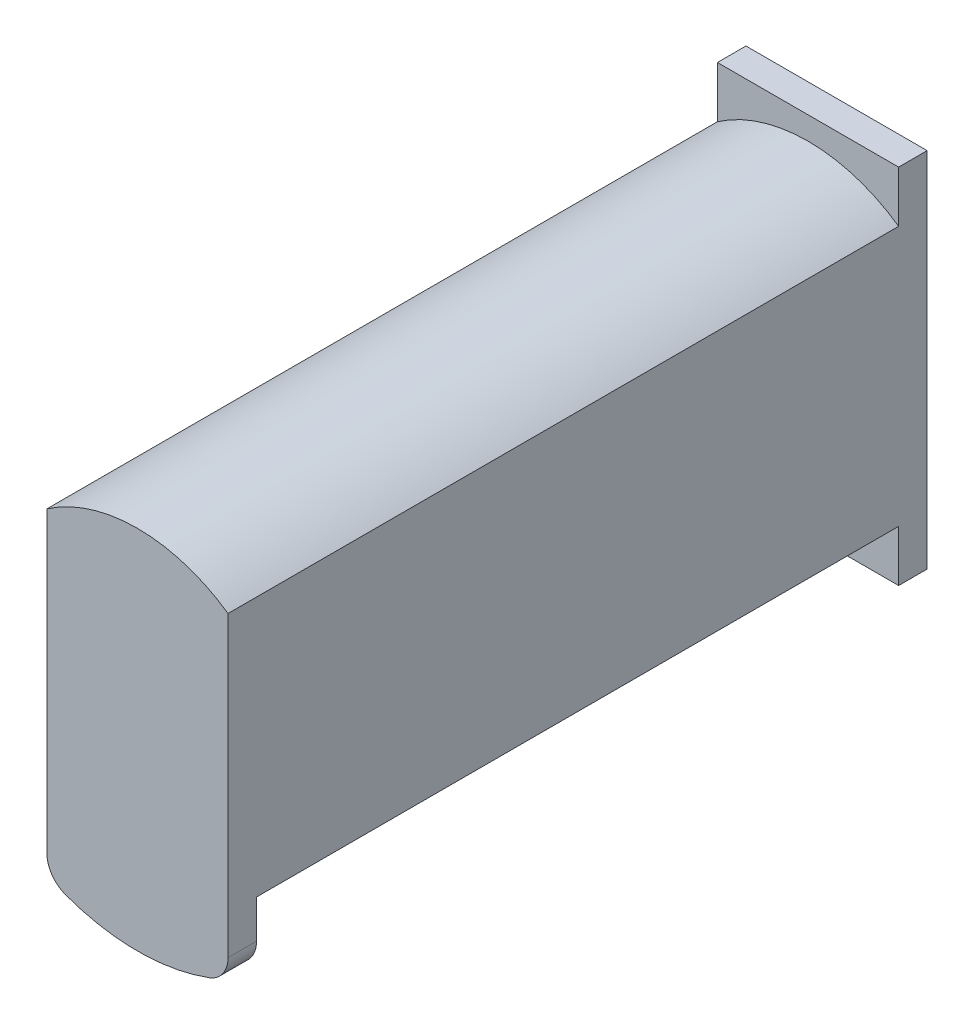
SolidWorks part; units mm, degrees
ref_plane "Front Plane" through (0, 0, 0) normal (0, 0, 1) x (1, 0, 0)
ref_plane "Top Plane" through (0, 0, 0) normal (0, 1, 0) x (1, 0, 0)
ref_plane "Right Plane" through (0, 0, 0) normal (1, 0, 0) x (0, 0, -1)
sketch "Sketch2" plane through (0, 0, 0) normal (0, 0, 1) x (1, 0, 0)
  line L0 (0, -12.7) -> (0, 12.7) construction
  line L1 (-12.7, -12.7) -> (-12.7, 12.7) construction
  line L2 (12.7, -12.7) -> (12.7, 12.7) construction
  line L6 (5.75, -6.2) -> (-5.75, -6.2)
  line L9 (5.75, -6.2) -> (5.75, -19.2)
  line L12 (5.75, -19.2) -> (-5.75, -19.2)
  line L15 (-12.7, 12.7) -> (12.7, 12.7)
  line L16 (12.7, -25.4) -> (-12.7, -25.4)
  line L17 (12.7, -25.4) -> (12.7, 25.4)
  line L18 (12.7, 25.4) -> (-12.7, 25.4)
  line L19 (-12.7, -25.4) -> (-12.7, 25.4)
  line L20 (12.7, -25.4) -> (-12.7, 25.4) construction
  line L21 (12.7, 25.4) -> (-12.7, -25.4) construction
  line L22 (-12.7, -12.7) -> (12.7, -12.7)
  line L23 (-5.75, -6.2) -> (-5.75, -19.2)
  line L24 (5.75, -6.2) -> (-5.75, -19.2) construction
  line L25 (5.75, -19.2) -> (-5.75, -6.2) construction
  line L26 (5.75, 19.2) -> (-5.75, 19.2)
  line L27 (5.75, 19.2) -> (5.75, 6.2)
  line L28 (5.75, 6.2) -> (-5.75, 6.2)
  line L29 (-5.75, 19.2) -> (-5.75, 6.2)
  line L30 (5.75, 19.2) -> (-5.75, 6.2) construction
  line L31 (5.75, 6.2) -> (-5.75, 19.2) construction
  arc A0 (-12.7, -12.7) -> (12.7, -12.7) centre (0, -12.7) ccw construction
  arc A1 (12.7, 12.7) -> (-12.7, 12.7) centre (0, 12.7) ccw construction
  circle A2 centre (0, 12.7) radius 3.5
  circle A3 centre (0, -12.7) radius 3.5
  arc A15 (-12.7, 18.2085) -> (12.7, 18.2085) centre (0, 0) cw
  arc A16 (-12.7, -18.2085) -> (12.7, -18.2085) centre (0, 0) ccw
  point P2 (0, 0)
  point P38 (0, 0)
  point P62 (0, 25.4)
  dimension "D3" = 7
  dimension "D4" = 13
  dimension "D5" = 11.5
  dimension "D11" = 69.79
  dimension "D12" = 22.2
  dimension "D13" = 22.2
  dimension "D1" = 25.4
  dimension "D2" = 25.4
extrude "Boss-Extrude4" add sketch "Sketch2" along normal blind 4 contours L18 L19 L16 L17 | A2 | A3
extrude "Boss-Extrude5" add sketch "Sketch2<4>" along normal blind 90 from surface contours L19 A16 L17 L22 L9 L12 L23 | A3 L22 L23 L12 L9 | A3 L22 L9 L6 L23 | L22 A3 | L22 A3 | L15 A2 | L15 A2 | A2 L15 L27 L26 L29 | A2 L15 L29 L28 L27 | L29 L15 L19 L22 L23 L6 L9 L17 L27 L28 | A15 L19 L15 L29 L26 L27 L17 region at (0, -8.8383, 0) region at (0, 0, 0) region at (9.225, -12.9712, 0) region at (0, -16.5617, 0) region at (0, -14.1854, 0) region at (0, -11.2146, 0) region at (9.225, 12.9712, 0) region at (0, 8.8383, 0) region at (0, 16.5617, 0) region at (0, 11.2146, 0) region at (0, 14.1854, 0) starting at face at (3.5, 12.7, 4)
sketch "Sketch2<4>" plane through (0, 0, 0) normal (0, 0, 1) x (1, 0, 0) same geometry as "Sketch2"
extrude "Cut-Extrude2" cut sketch "Sketch2<6>" along normal blind 6 from offset 8 contours L6 L23 L12 L9 | L28 L29 L26 L27
sketch "Sketch2<6>" plane through (0, 0, 0) normal (0, 0, 1) x (1, 0, 0) same geometry as "Sketch2"
extrude "Cut-Extrude3" cut sketch "Sketch2<7>" along normal blind 25 contours A2 | A3
sketch "Sketch2<7>" plane through (0, 0, 0) normal (0, 0, 1) x (1, 0, 0) same geometry as "Sketch2"
sketch "Sketch3" plane through (0, 0, 94) normal (0, 0, 1) x (1, 0, 0)
  line L0 (12.7, -18.2085) -> (12.7, -26.2085)
  line L2 (12.7, -18.2085) -> (12.7, 18.2085)
  line L3 (-12.7, 18.2085) -> (-12.7, -18.2085)
  line L4 (12.7, -18.2085) -> (12.7, 18.2085)
  line L5 (-12.7, 18.2085) -> (-12.7, -18.2085)
  line L6 (-12.7, -26.2085) -> (-12.7, -18.2085)
  arc A1 (12.7, -26.2085) -> (-12.7, -26.2085) centre (0, 0) cw
  arc A2 (-12.7, -18.2085) -> (12.7, -18.2085) centre (0, 0) ccw
  arc A3 (12.7, 18.2085) -> (-12.7, 18.2085) centre (0, 0) ccw
  arc A5 (12.7, 18.2085) -> (-12.7, 18.2085) centre (0, 0) ccw
  point P9 (-13.2372, -47.7851)
  dimension "D2" = 8
  dimension "D1" = 0
extrude "Boss-Extrude6" add sketch "Sketch3" along normal blind 4
fillet "Fillet1" radius 4 2 edges at (-12.7, -26.2085, 96) (12.7, -26.2085, 96)
